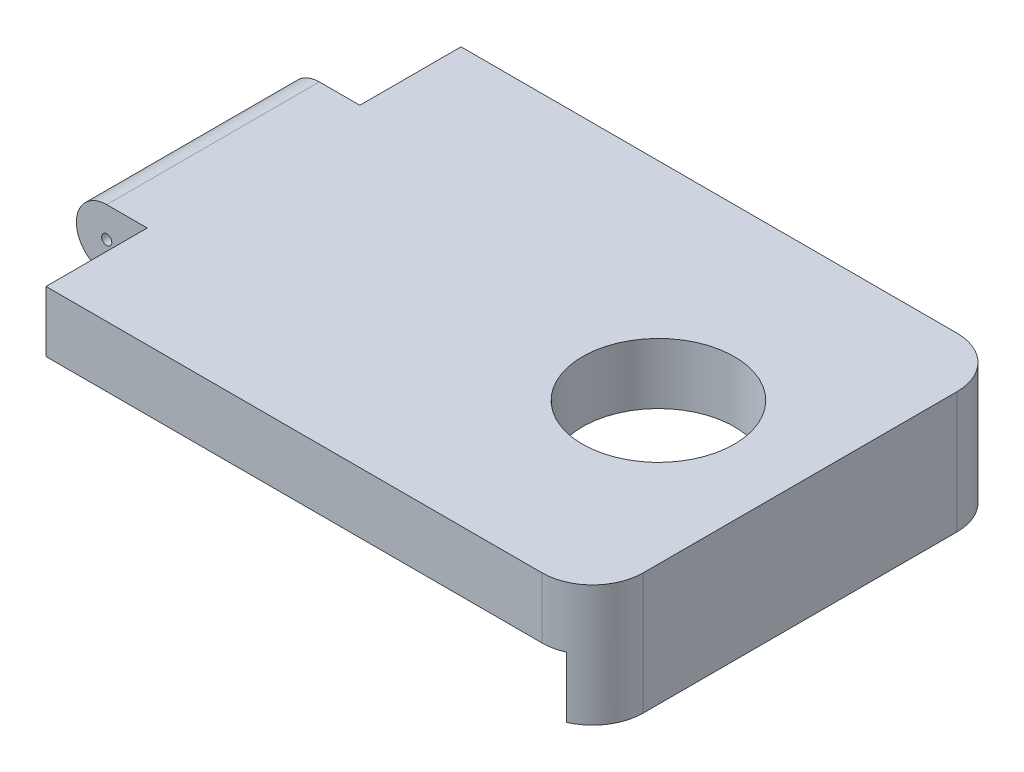
SolidWorks part; units mm, degrees
material "Hexcel AS4C (3000 волосков)"
ref_plane "Спереди" through (0, 0, 0) normal (0, 0, 1) x (1, 0, 0)
ref_plane "Сверху" through (0, 0, 0) normal (0, 1, 0) x (1, 0, 0)
ref_plane "Справа" through (0, 0, 0) normal (1, 0, 0) x (0, 0, -1)
sketch "Эскиз1" plane through (0, 0, 0) normal (0, 1, 0) x (1, 0, 0)
  line L0 (-27, 0) -> (-27, -10.5) construction
  line L1 (-27, -20.5) -> (27, -20.5)
  line L2 (-27, -20.5) -> (-27, 20.5) construction
  line L3 (-27, 20.5) -> (27, 20.5)
  line L4 (27, -20.5) -> (27, 20.5)
  line L5 (-27, -20.5) -> (27, 20.5) construction
  line L6 (-27, 20.5) -> (27, -20.5) construction
  line L7 (-27, -10.5) -> (-34, -10.5)
  line L8 (-34, -10.5) -> (-34, 10.5)
  line L9 (-34, 10.5) -> (-27, 10.5)
  line L10 (-27, 10.5) -> (-27, 20.5)
  line L11 (-27, -10.5) -> (-27, -20.5)
  line L12 (-27, 10.5) -> (-27, -10.5) construction
  point P0 (0, 0)
  dimension "D1" = 54
  dimension "D2" = 41
  dimension "D3" = 21
  dimension "D4" = 7
extrude "Бобышка-Вытянуть1" add sketch "Эскиз1" along normal blind 6
fillet "Скругление1" 2 edges at (-34, 6, 0) (-34, 0, 0) type full round first side face at (-15.25, 6, 0) second side face at (-15.25, 0, 0) middle face at (-34, 3, 0) tangent propagation no
sketch "Эскиз2" plane through (0, 6, 0) normal (0, 1, 0) x (1, 0, 0)
  line L0 (-27, 10.5) -> (13, 10.5) construction
  line L1 (13, 10.5) -> (13, 0) construction
  circle A0 centre (13, 0) radius 7.5
extrude "Вырез-Вытянуть1" cut sketch "Эскиз2" against normal blind 6
fillet "Скругление2" radius 5 1 edges at (27, 3, -20.5) type face fillet first side face at (27, 3, 0) second side face at (0, 3, -20.5)
fillet "Скругление3" radius 5 1 edges at (27, 3, 20.5) type face fillet first side face at (27, 3, 2.5) second side face at (0, 3, 20.5)
sketch "Эскиз3" plane through (0, 0, 0) normal (0, -1, 0) x (1, 0, 0)
  line L0 (27, 15.5) -> (24, 15.5) construction
  line L1 (24, 15.5) -> (24, -20.0826)
  line L2 (24, 15.5) -> (24, 20.0826)
  line L3 (27, 15.5) -> (27, -15.5)
  arc A0 (22, -20.5) -> (27, -15.5) centre (22, -15.5) ccw construction
  arc A1 (27, 15.5) -> (22, 20.5) centre (22, 15.5) ccw construction
  arc A2 (24, 20.0826) -> (27, 15.5) centre (22, 15.5) cw
  arc A3 (27, -15.5) -> (24, -20.0826) centre (22, -15.5) cw
  dimension "D1" = 3
extrude "Бобышка-Вытянуть2" add sketch "Эскиз3" along normal blind 6
sketch "Эскиз4" plane through (0, 0, 10.5) normal (0, 0, 1) x (1, 0, 0)
  line L0 (-31, 6) -> (-31, 0) construction
  circle A0 centre (-31, 3) radius 0.5
extrude "Вырез-Вытянуть2" cut sketch "Эскиз4" against normal up to surface (21 mm away) up to face at (-29.75, 3, -10.5)
